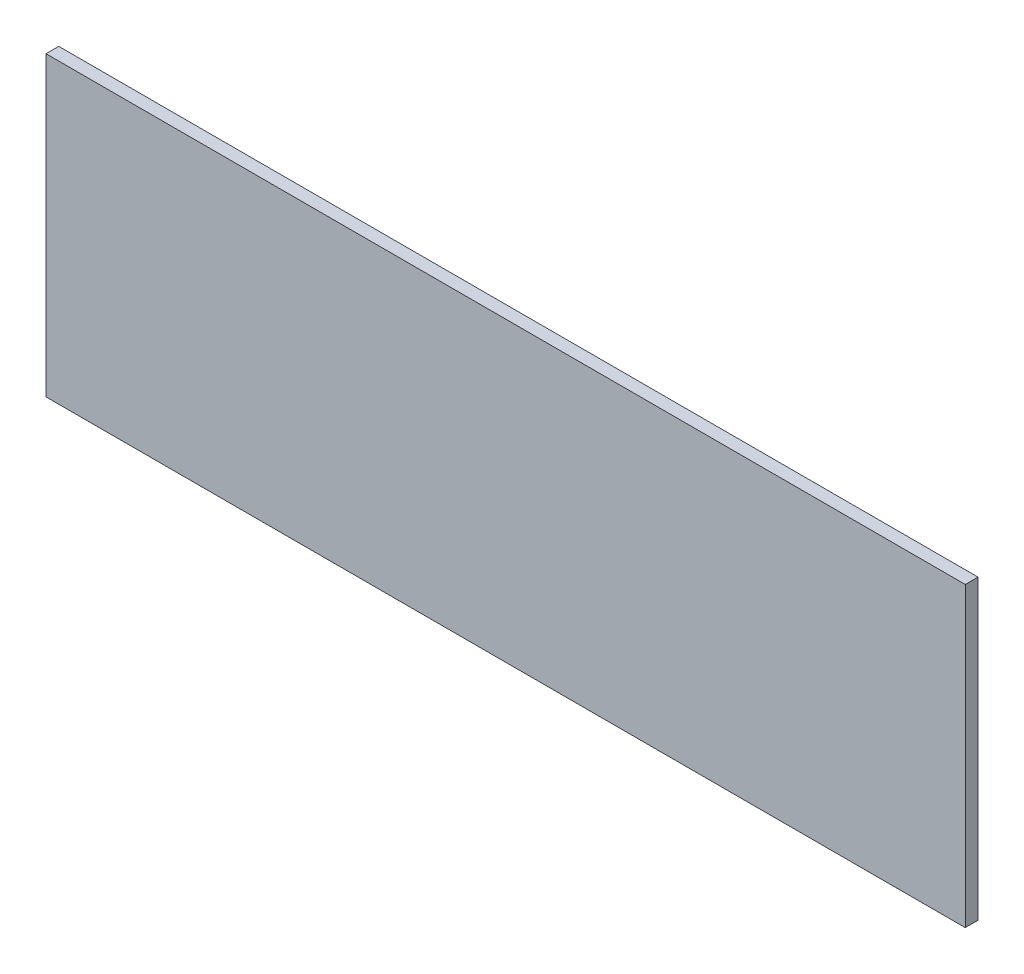
SolidWorks part; units mm, degrees
ref_plane "Front Plane" through (0, 0, 0) normal (0, 0, 1) x (1, 0, 0)
ref_plane "Top Plane" through (0, 0, 0) normal (0, 1, 0) x (1, 0, 0)
ref_plane "Right Plane" through (0, 0, 0) normal (1, 0, 0) x (0, 0, -1)
sketch "Sketch1" plane through (0, 0, 0) normal (0, 0, 1) x (1, 0, 0)
  line L1 (6, 250) -> (439, 250)
  line L2 (6, 250) -> (6, 110)
  line L3 (6, 110) -> (439, 110)
  line L4 (439, 250) -> (439, 110)
extrude "Boss-Extrude1" add sketch "Sketch1" against normal blind 6 contours L2 L3 L4 L1
